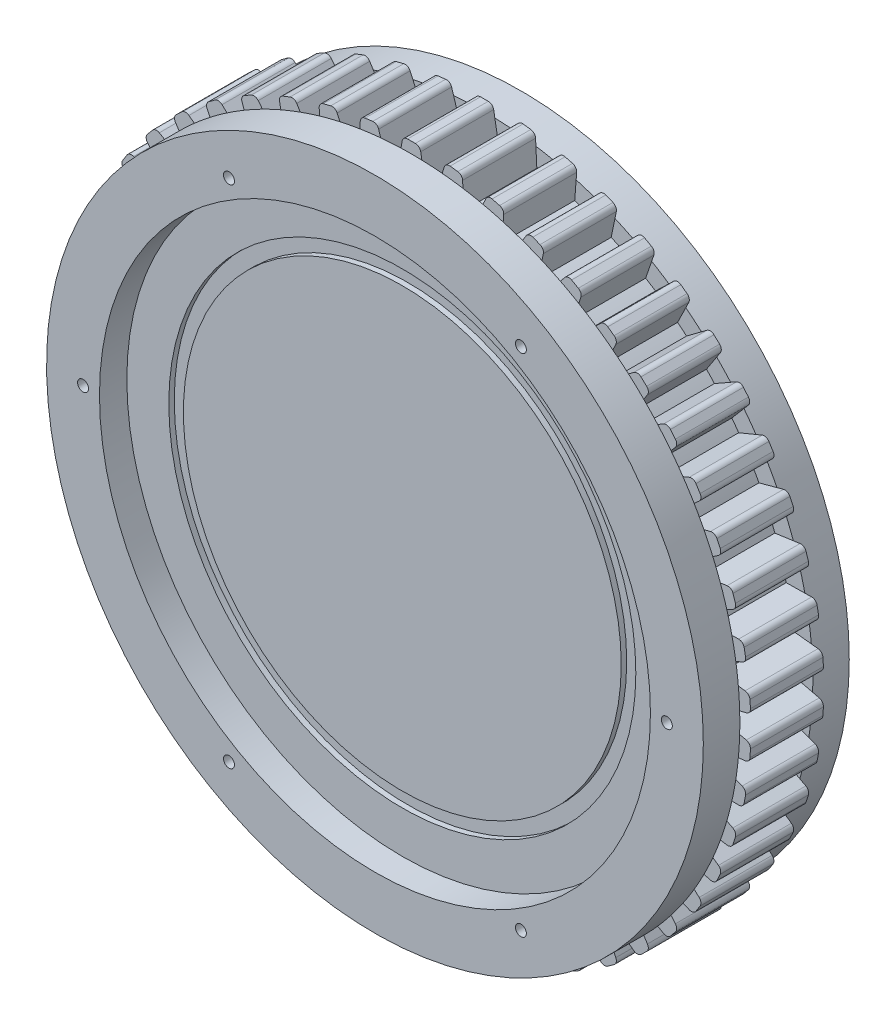
SolidWorks part; units mm, degrees
ref_plane "Plan de face" through (0, 0, 0) normal (0, 0, 1) x (1, 0, 0)
ref_plane "Plan de dessus" through (0, 0, 0) normal (0, 1, 0) x (1, 0, 0)
ref_plane "Plan de droite" through (0, 0, 0) normal (1, 0, 0) x (0, 0, -1)
sketch "Esquisse1" plane through (0, 0, 0) normal (0, 0, 1) x (1, 0, 0)
  circle A1 centre (0, 0) radius 90
  dimension "D2" = 180
extrude "Boss.-Extru.2" add sketch "Esquisse1" along normal blind 40
sketch "Esquisse2" plane through (0, 0, 40) normal (0, 0, 1) x (1, 0, 0)
  circle A0 centre (0, 0) radius 75.5
  dimension "D1" = 151
extrude "Enlèv. mat.-Extru.1" cut sketch "Esquisse2" against normal blind 7.5
sketch "Esquisse3" plane through (0, 0, 32.5) normal (0, 0, 1) x (1, 0, 0)
  circle A0 centre (0, 0) radius 60
  circle A1 centre (0, 0) radius 64
  dimension "D1" = 120
  dimension "D2" = 128
extrude "Enlèv. mat.-Extru.2" cut sketch "Esquisse3" against normal blind 1.5
shell "Coque1" thickness 10 removed face at (90, 0, 0)
sketch "Esquisse5" plane through (0, 0, 0) normal (1, 0, 0) x (0, 0, -1)
  line L0 (0, 0) -> (-74.4042, 0) construction
sketch "Esquisse4" plane through (0, 0, 0) normal (1, 0, 0) x (0, 0, -1)
  line L0 (-10, -90) -> (-10, -85)
  line L1 (-40, -90) -> (0, -90) construction
  line L2 (-10, -85) -> (-30, -85)
  line L3 (-30, -85) -> (-30, -90)
  line L4 (-30, -90) -> (-10, -90)
  line L5 (0, -90) -> (0, 90) construction
  line L6 (-40, 90) -> (-40, -90) construction
  point P8 (-30, -87.5)
  dimension "D1" = 10
  dimension "D2" = 10
  dimension "D3" = 5
revolve "Enlèvement de matière-Révolution1" cut sketch "Esquisse4" angle 360 about L0
sketch "Esquisse7" plane through (0, 0, 40) normal (0, 0, 1) x (1, 0, 0)
  circle A0 centre (80, 0) radius 1.5
  dimension "D1" = 3
  dimension "D2" = 80
extrude "Enlèv. mat.-Extru.4" cut sketch "Esquisse7" against normal blind 10
pattern_circular "Répétition circulaire2" count 6 over 360 about axis through (0, 0, 0) along (0, 0, 1) of "Enlèv. mat.-Extru.4" reverse direction yes
sketch "Esquisse8" plane through (0, 0, 0) normal (1, 0, 0) x (0, 0, -1)
  line L0 (-10, 83.0257) -> (-30, 83.0257)
  line L1 (-10, 85) -> (-10, -85) construction
  line L2 (-30, -90) -> (-30, 90) construction
  line L3 (-30, 83.0257) -> (-30, 93.0257)
  line L4 (-30, 93.0257) -> (-10, 93.0257)
  line L5 (-10, 93.0257) -> (-10, 83.0257)
  line L6 (-30, 90) -> (-40, 90) construction
  point P7 (-20, 93.0257)
  point P9 (-20, 83.0257)
  dimension "D1" = 20
  dimension "D2" = 10
  dimension "D3" = 3.0257
extrude "Boss.-Extru.3" add sketch "Esquisse8" along normal mid plane 7.5
sketch "Esquisse9" plane through (0, 0, 30) normal (0, 0, 1) x (1, 0, 0)
  line L0 (-3.75, 84.9172) -> (-2.3203, 93.0257)
  line L1 (3.75, 93.0257) -> (-3.75, 93.0257) construction
  line L3 (2.3203, 93.0257) -> (3.75, 84.9172)
  line L4 (-3.75, 89.9218) -> (-3.75, 84.9172) construction
  line L6 (3.75, 93.0257) -> (3.75, 89.9218) construction
  line L7 (-3.75, 84.9172) -> (-3.75, 93.0257)
  line L8 (-3.75, 93.0257) -> (-2.3203, 93.0257)
  line L9 (3.75, 84.9172) -> (3.75, 93.0257)
  line L10 (3.75, 93.0257) -> (2.3203, 93.0257)
  dimension "D1" = 10
  dimension "D2" = 10
extrude "Enlèv. mat.-Extru.6" cut sketch "Esquisse9" against normal up to surface (20 mm away) up to face at (0, -0.0402, 10)
fillet "Congé1" radius 1.5 2 edges at (2.3203, 93.0257, 20) (-2.3203, 93.0257, 20)
pattern_circular "Répétition circulaire3" count 50 over 360 about axis through (0, 0, 0) along (0, 0, 1) of "Boss.-Extru.3", "Enlèv. mat.-Extru.6", "Congé1" reverse direction yes
sketch "Esquisse10" plane through (0, 0, 22.5) normal (0, 0, -1) x (-1, 0, 0)
  circle A0 centre (-22.5, 30) radius 6.25
  dimension "D3" = 12.5
  dimension "D1" = 30
  dimension "D2" = 22.5
extrude "Boss.-Extru.4" add sketch "Esquisse10" along normal blind 22.5
sketch "Esquisse11" plane through (0, 0, 0) normal (0, 0, -1) x (-1, 0, 0)
  circle A0 centre (-22.5, 30) radius 2.25
  dimension "D1" = 4.5
extrude "Enlèv. mat.-Extru.7" cut sketch "Esquisse11" against normal blind 11.25
mirror "Symétrie1" about plane through (0, 0, 0) normal (1, 0, 0) of "Enlèv. mat.-Extru.7", "Boss.-Extru.4"
mirror "Symétrie2" about plane through (0, 0, 0) normal (0, 1, 0) of "Symétrie1"
